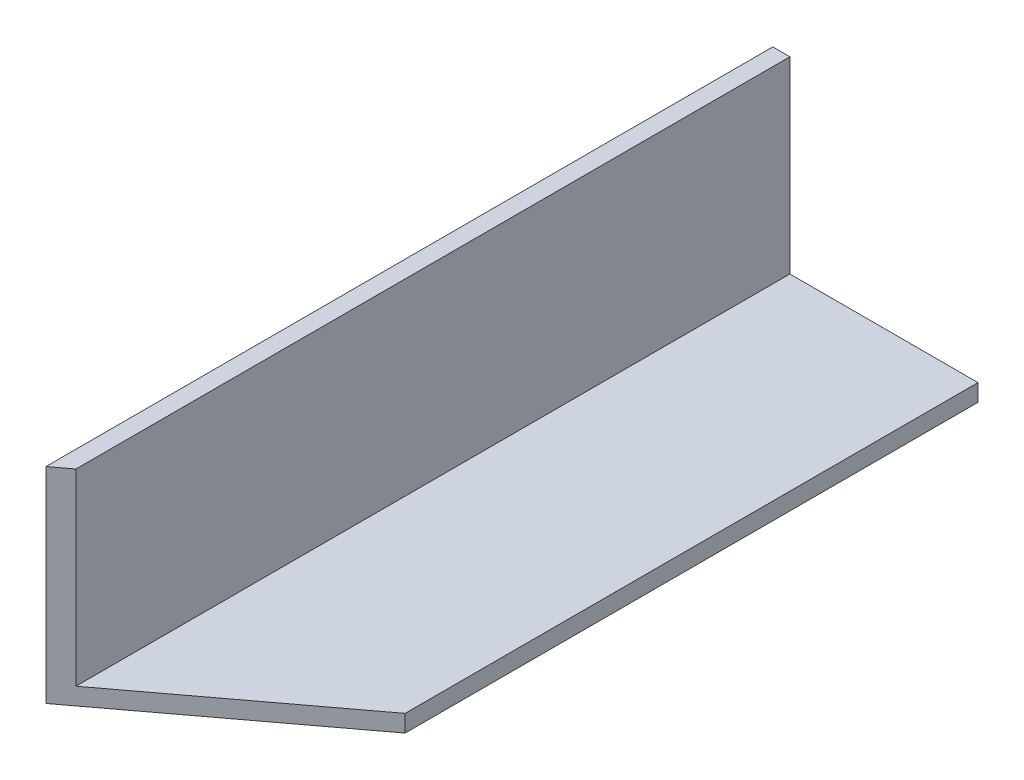
SolidWorks part; units mm, degrees
ref_plane "Front Plane" through (0, 0, 0) normal (0, 0, 1) x (1, 0, 0)
ref_plane "Top Plane" through (0, 0, 0) normal (0, 1, 0) x (1, 0, 0)
ref_plane "Right Plane" through (0, 0, 0) normal (1, 0, 0) x (0, 0, -1)
sketch "Sketch1" plane through (0, 0, 0) normal (0, 0, 1) x (1, 0, 0)
  line L1 (0, 0) -> (38.1, 0)
  line L2 (0, 0) -> (0, 38.1)
  line L3 (0, 38.1) -> (38.1, 38.1)
  line L4 (38.1, 0) -> (38.1, 38.1)
extrude "Boss-Extrude1" add sketch "Sketch1" along normal blind 134.9377
sketch "Sketch2" plane through (0, 0, 134.9377) normal (0, 0, 1) x (1, 0, 0)
  line L1 (38.1, 38.1) -> (3.175, 38.1)
  line L2 (38.1, 38.1) -> (38.1, 3.175)
  line L3 (38.1, 3.175) -> (3.175, 3.175)
  line L4 (3.175, 38.1) -> (3.175, 3.175)
extrude "Cut-Extrude1" cut sketch "Sketch2" against normal blind 134.9377
sketch "Sketch4" plane through (0, 0, 0) normal (0, -1, 0) x (-1, 0, 0)
  line L0 (0, -134.9377) -> (-38.1, -106.3626)
  line L1 (-38.1, -134.9377) -> (-38.1, 0) construction
  line L2 (-38.1, -106.3626) -> (-38.1, -134.9377)
  line L3 (-38.1, -134.9377) -> (0, -134.9377)
  point P5 (-38.1, -103.7446)
  dimension "D1" = 36.87
extrude "Cut-Extrude2" cut sketch "Sketch4" against normal blind 38.1
